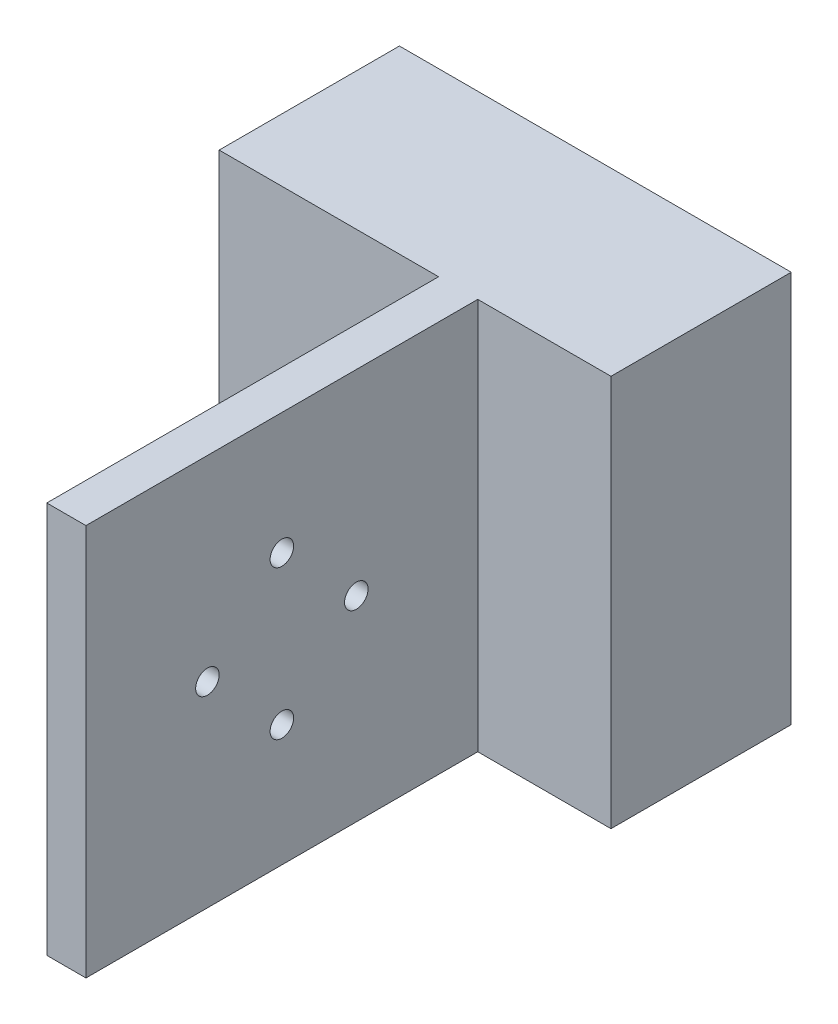
SolidWorks part; units mm, degrees
ref_plane "Front Plane" through (0, 0, 0) normal (0, 0, 1) x (1, 0, 0)
ref_plane "Top Plane" through (0, 0, 0) normal (0, 1, 0) x (1, 0, 0)
ref_plane "Right Plane" through (0, 0, 0) normal (1, 0, 0) x (0, 0, -1)
sketch "Sketch1" plane through (0, 0, 0) normal (1, 0, 0) x (0, -1, 0)
  line L1 (-25, 25) -> (25, 25)
  line L2 (-25, 25) -> (-25, -25)
  line L3 (-25, -25) -> (25, -25)
  line L4 (25, 25) -> (25, -25)
  line L5 (-25, 25) -> (25, -25) construction
  line L6 (-25, -25) -> (25, 25) construction
  circle A1 centre (0, 0) radius 9.5 construction
  circle A2 centre (0, 9.5) radius 1.5
  circle A3 centre (9.5, 0) radius 1.5
  circle A4 centre (0, -9.5) radius 1.5
  circle A5 centre (-9.5, 0) radius 1.5
  point P0 (0, 0)
  point P19 (0, 0)
  dimension "D1" = 19
  dimension "D2" = 3
  dimension "D5" = 25
  dimension "D3" = 25
  dimension "D4" = 4
extrude "Boss-Extrude1" add sketch "Sketch1" along normal blind 5
sketch "Sketch2" plane through (0, 0, -25) normal (0, 0, -1) x (-1, 0, 0)
  line L0 (-22, 25) -> (28, 25)
  line L1 (28, 25) -> (28, -25)
  line L2 (28, -25) -> (-22, -25)
  line L3 (-22, -25) -> (-22, 25)
  line L4 (-5, -25) -> (-5, 25) construction
  dimension "D1" = 50
  dimension "D2" = 17
extrude "Boss-Extrude2" add sketch "Sketch2" along normal blind 5
sketch "Sketch3" plane through (0, 0, -30) normal (0, 0, -1) x (-1, 0, 0)
  line L0 (-22, 25) -> (-22, -25)
  line L1 (-22, -25) -> (28, -25)
  line L2 (28, -25) -> (28, 25)
  line L3 (28, 25) -> (-22, 25)
  line L4 (-22, 25) -> (28, -25) construction
  line L5 (-22, -25) -> (28, 25) construction
  line L6 (-22, 25) -> (-22, -25) construction
  circle A0 centre (3, 0) radius 6
  dimension "D1" = 12
extrude "Boss-Extrude3" add sketch "Sketch3" along normal blind 18
equation "\"ShaftDiameter\"= 12mm"
equation "\"PendulumDiameter\"=12mm"
equation "\"PendulumLength\"= 140mm"
equation "\"D1@Sketch3\"=\"PendulumDiameter\""
